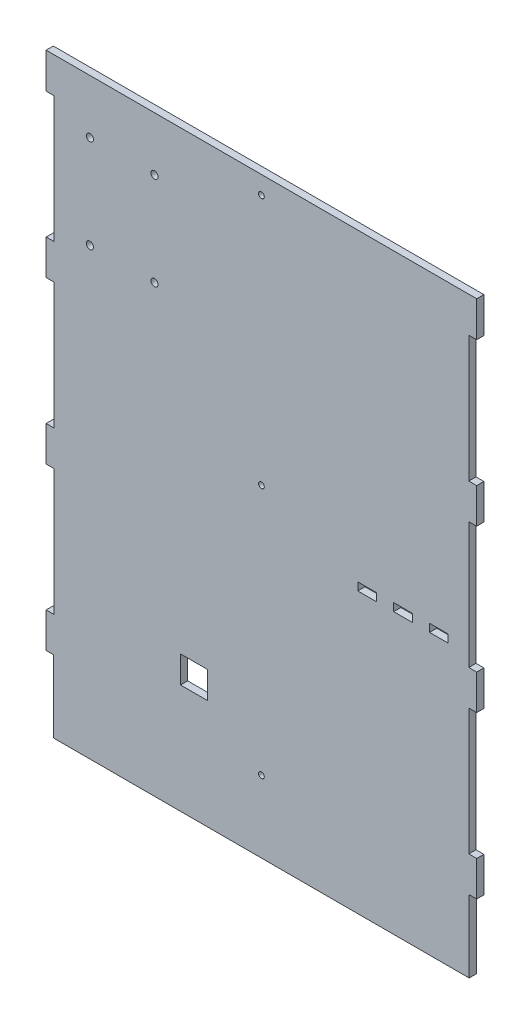
SolidWorks part; units mm, degrees
ref_plane "Front Plane" through (0, 0, 0) normal (0, 0, 1) x (1, 0, 0)
ref_plane "Top Plane" through (0, 0, 0) normal (0, 1, 0) x (1, 0, 0)
ref_plane "Right Plane" through (0, 0, 0) normal (1, 0, 0) x (0, 0, -1)
sketch "Sketch1" plane through (0, 0, 0) normal (0, 0, 1) x (1, 0, 0)
  line L1 (-130.9091, 180) -> (109.0909, 180)
  line L2 (-130.9091, 180) -> (-130.9091, -150)
  line L3 (-130.9091, -150) -> (109.0909, -150)
  line L4 (109.0909, 180) -> (109.0909, -150)
  line L5 (-130.9091, 180) -> (109.0909, -150) construction
  line L6 (-130.9091, -150) -> (109.0909, 180) construction
  point P0 (0, 0)
  dimension "D1" = 240
extrude "Boss-Extrude1" add sketch "Sketch1" along normal blind 4
sketch "Sketch2" plane through (0, 0, 0) normal (0, 0, -1) x (-1, 0, 0)
  line L0 (130.9091, 180) -> (130.9091, -150) construction
  line L1 (126.5091, 160.2) -> (130.9091, 160.2)
  line L2 (126.5091, 160.2) -> (126.5091, 89.8)
  line L3 (126.5091, 89.8) -> (130.9091, 89.8)
  line L4 (130.9091, 160.2) -> (130.9091, 89.8)
  line L5 (126.7091, -110) -> (130.7091, -110) construction
  line L6 (126.5091, 70.2) -> (130.9091, 70.2)
  line L7 (126.5091, 70.2) -> (126.5091, -0.2)
  line L8 (126.5091, -0.2) -> (130.9091, -0.2)
  line L9 (130.9091, 70.2) -> (130.9091, -0.2)
  line L10 (126.5091, -19.8) -> (130.9091, -19.8)
  line L11 (126.5091, -19.8) -> (126.5091, -90.2)
  line L12 (126.5091, -90.2) -> (130.9091, -90.2)
  line L13 (130.9091, -19.8) -> (130.9091, -90.2)
  line L14 (126.7091, -109.8) -> (130.9091, -109.8)
  line L15 (126.7091, -109.8) -> (126.7091, -150)
  line L16 (126.7091, -150) -> (130.9091, -150)
  line L17 (130.9091, -109.8) -> (130.9091, -150)
  line L18 (126.7091, -90) -> (130.7091, -90) construction
  line L19 (126.7091, -90) -> (126.7091, -20) construction
  line L20 (126.7091, -20) -> (130.7091, -20) construction
  line L21 (126.7091, 0) -> (130.7091, 0) construction
  line L22 (126.7091, 0) -> (126.7091, 70) construction
  line L23 (126.7091, 70) -> (130.7091, 70) construction
  line L24 (126.7091, 90) -> (130.7091, 90) construction
  line L25 (126.7091, 90) -> (126.7091, 160) construction
  line L26 (126.7091, 160) -> (130.7091, 160) construction
  line L27 (10.9091, 180) -> (10.9091, -150) construction
  line L28 (-109.0909, 180) -> (130.9091, 180) construction
  line L29 (130.9091, -150) -> (-109.0909, -150) construction
  line L30 (-109.0909, -109.8) -> (-109.0909, -150)
  line L31 (-104.8909, -150) -> (-109.0909, -150)
  line L32 (-104.8909, -109.8) -> (-104.8909, -150)
  line L33 (-104.8909, -109.8) -> (-109.0909, -109.8)
  line L34 (-109.0909, -19.8) -> (-109.0909, -90.2)
  line L35 (-104.6909, -90.2) -> (-109.0909, -90.2)
  line L36 (-104.6909, -19.8) -> (-104.6909, -90.2)
  line L37 (-104.6909, -19.8) -> (-109.0909, -19.8)
  line L38 (-109.0909, 70.2) -> (-109.0909, -0.2)
  line L39 (-104.6909, -0.2) -> (-109.0909, -0.2)
  line L40 (-104.6909, 70.2) -> (-104.6909, -0.2)
  line L41 (-104.6909, 70.2) -> (-109.0909, 70.2)
  line L42 (-109.0909, 160.2) -> (-109.0909, 89.8)
  line L43 (-104.6909, 89.8) -> (-109.0909, 89.8)
  line L44 (-104.6909, 160.2) -> (-104.6909, 89.8)
  line L45 (-104.6909, 160.2) -> (-109.0909, 160.2)
  dimension "D1" = 4.2
  dimension "D2" = 0.2
  dimension "D3" = 0.2
  dimension "D4" = 0.2
  dimension "D5" = 0.2
  dimension "D6" = 0.2
  dimension "D7" = 0.2
  dimension "D8" = 0.2
  dimension "D9" = 0.2
  dimension "D10" = 0.2
  dimension "D11" = 0.2
extrude "Cut-Extrude1" cut sketch "Sketch2" against normal through all
sketch "Sketch3" plane through (0, 0, 0) normal (0, 0, -1) x (-1, 0, 0)
  line L0 (126.5091, -19.8) -> (126.5091, -90.2) construction
  line L1 (41.0091, -74) -> (56.0091, -74)
  line L2 (41.0091, -74) -> (41.0091, -89)
  line L3 (41.0091, -89) -> (56.0091, -89)
  line L4 (56.0091, -74) -> (56.0091, -89)
  line L5 (126.7091, -150) -> (-104.8909, -150) construction
  point P7 (126.5091, -55)
  dimension "D1" = 15
  dimension "D2" = 15
  dimension "D3" = 70.5
  dimension "D4" = 61
extrude "Cut-Extrude2" cut sketch "Sketch3" against normal through all
sketch "Sketch4" plane through (0, 0, 4) normal (0, 0, 1) x (1, 0, 0)
  line L1 (109.0909, 180) -> (-130.9091, 180) construction
  circle A1 centre (-10.9091, 170) radius 1.6
  circle A2 centre (-10.9091, 30) radius 1.6
  circle A3 centre (-10.9091, -110) radius 1.6
  point P4 (-10.9091, 180)
  dimension "D2" = 3.2
  dimension "D1" = 10
  dimension "D3" = 3
extrude "Cut-Extrude3" cut sketch "Sketch4" against normal through all
sketch "Sketch5" plane through (0, 0, 4) normal (0, 0, 1) x (1, 0, 0)
  line L0 (109.0909, 180) -> (-130.9091, 180) construction
  line L1 (-126.5091, 160.2) -> (-126.5091, 89.8) construction
  line L2 (-10.9091, 180) -> (-10.9091, -150) construction
  line L3 (-126.7091, -150) -> (104.8909, -150) construction
  circle A0 centre (-106.5091, 150) radius 2
  circle A1 centre (-70.5091, 150) radius 2
  circle A2 centre (-106.5091, 98) radius 2
  circle A3 centre (-70.5091, 98) radius 2
  dimension "D1" = 52
  dimension "D3" = 4
  dimension "D2" = 36
  dimension "D4" = 30
  dimension "D5" = 20
extrude "Cut-Extrude4" cut sketch "Sketch5" against normal through all
sketch "Sketch6" plane through (0, 0, 0) normal (0, 0, -1) x (-1, 0, 0)
  line L0 (-93.1909, 10.2) -> (-82.7909, 10.2)
  line L1 (-92.9909, 10) -> (-82.9909, 10)
  line L2 (-92.9909, 10) -> (-92.9909, 6)
  line L3 (-92.9909, 6) -> (-82.9909, 6)
  line L4 (-82.9909, 10) -> (-82.9909, 6)
  line L5 (-82.7909, 10.2) -> (-82.7909, 5.8)
  line L6 (-93.1909, 5.8) -> (-82.7909, 5.8)
  line L7 (-93.1909, 10.2) -> (-93.1909, 5.8)
  line L8 (-73.1909, 5.8) -> (-62.7909, 5.8)
  line L9 (-73.1909, 10.2) -> (-73.1909, 5.8)
  line L10 (-73.1909, 10.2) -> (-62.7909, 10.2)
  line L11 (-62.7909, 10.2) -> (-62.7909, 5.8)
  line L12 (-53.1909, 5.8) -> (-42.7909, 5.8)
  line L13 (-53.1909, 10.2) -> (-53.1909, 5.8)
  line L14 (-53.1909, 10.2) -> (-42.7909, 10.2)
  line L15 (-42.7909, 10.2) -> (-42.7909, 5.8)
  dimension "D1" = 0.2
  dimension "D2" = 3
extrude "Cut-Extrude5" cut sketch "Sketch6" against normal blind 4 contours L11 L10 L9 L8 | L15 L14 L13 L12 | L0 L7 L6 L5 L1 L4 L3 L2 | L4 L1 L2 L3 region at (87.9909, 10.0871, 0) region at (87.9909, 8, 0) region at (67.9909, 8, 0) region at (47.9909, 8, 0)
